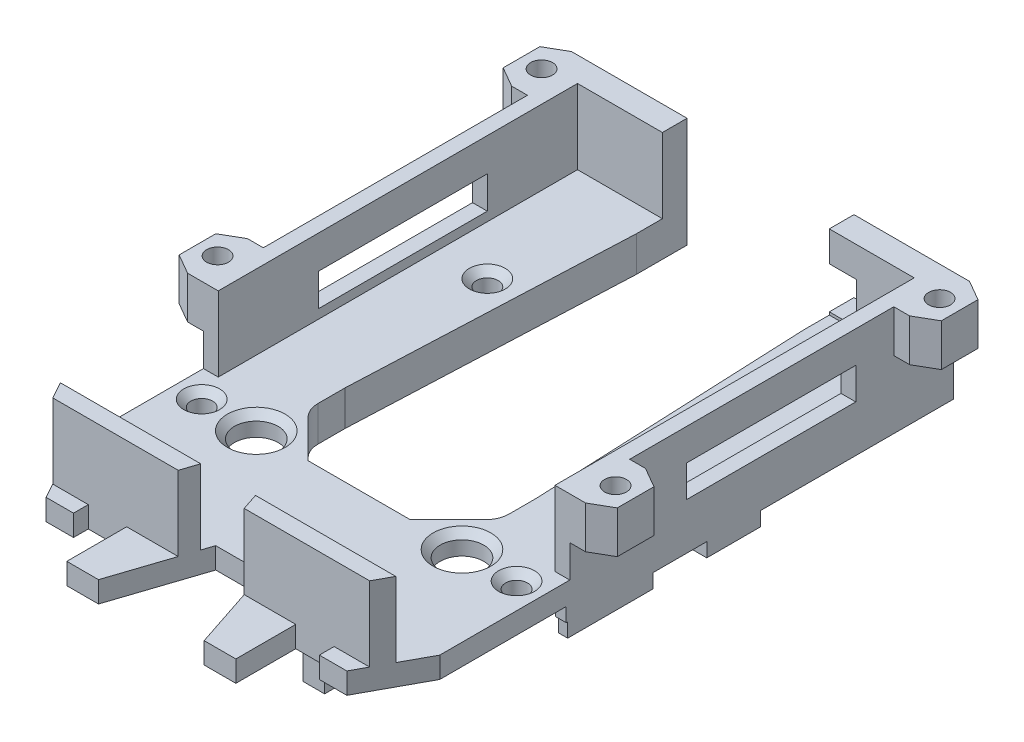
SolidWorks part; units mm, degrees
other "细节项目1"
material "PPS"
ref_plane "前视基准面" through (0, 0, 0) normal (0, 0, 1) x (1, 0, 0)
ref_plane "上视基准面" through (0, 0, 0) normal (0, 1, 0) x (1, 0, 0)
ref_plane "右视基准面" through (0, 0, 0) normal (1, 0, 0) x (0, 0, -1)
sketch "轮廓参考-草图" plane through (0, 0, 0) normal (0, 1, 0) x (1, 0, 0)
  line L0 (-126.4995, 0) -> (116.8967, 0) construction
  line L2 (0, 104.5414) -> (0, -99.6328) construction
  line L25 (24.5, -95.1) -> (26.0011, -95.1) construction
  line L38 (-16.7464, -105.1066) -> (-17.9066, -103.9464) construction
  line L42 (26.0011, -95.1) -> (26.0011, -102.35)
  line L72 (26.0011, -102.35) -> (22.5, -102.35)
  line L80 (-18.6137, -103.9464) -> (-19.7036, -105.0363) construction
  line L82 (4.1009, -74) -> (4.1009, -71.0475)
  line L83 (-3.6009, -74.5) -> (3.6009, -74.5)
  line L86 (-4.1009, -74) -> (-4.1009, -71.0461)
  line L88 (-4.8984, -70.3461) -> (-4.8009, -70.3461)
  line L91 (4.8009, -70.3475) -> (4.8984, -70.3475)
  line L98 (19, -100.5) -> (-19, -100.5) construction
  line L100 (22.5, -102.35) -> (22.5, -110.35)
  line L101 (16.1, -146) -> (16.1, -154.5)
  line L102 (16.1, -146) -> (12, -146)
  line L103 (12, -146) -> (12, -163)
  line L104 (17.45, -154.5) -> (16.1, -154.5)
  line L105 (17.45, -156.6) -> (17.45, -154.5)
  line L106 (-3.3584, -150.5) -> (-7.5, -163)
  line L107 (-7.5, -163) -> (-12, -163)
  line L108 (21.3534, -156.6) -> (17.45, -156.6)
  line L109 (-17.45, -156.6) -> (-17.45, -154.5)
  line L110 (-17.45, -154.5) -> (-16.1, -154.5)
  line L111 (-12, -146) -> (-12, -163)
  line L112 (-16.1, -146) -> (-12, -146)
  line L113 (-16.1, -146) -> (-16.1, -154.5)
  line L114 (7.5, -163) -> (12, -163)
  line L115 (-3.3584, -150.5) -> (3.3584, -150.5)
  line L116 (3.3584, -150.5) -> (7.5, -163)
  line L117 (-21.3534, -156.6) -> (-17.45, -156.6)
  line L118 (-13.5761, -121.8546) -> (-11.8487, -82.2911)
  line L119 (-12.5918, -128.1539) -> (-7.25, -133.5)
  line L120 (-7.25, -133.5) -> (7.25, -133.5)
  line L121 (-13.5793, -125.7684) -> (-13.5793, -122.0018)
  line L122 (22.5, -110.35) -> (26.0011, -110.35)
  line L123 (26.0011, -130.1) -> (26.0011, -148.0463)
  line L124 (26.0011, -148.0463) -> (21.3534, -156.6)
  line L125 (-26.0011, -148.0463) -> (-21.3534, -156.6)
  line L126 (-26.0011, -130.1) -> (-26.0011, -148.0463)
  line L127 (26.0011, -110.35) -> (26.0011, -117.6)
  line L128 (26.0011, -117.6) -> (24.5011, -117.6)
  line L129 (24.5011, -117.6) -> (24.5011, -130.1)
  line L130 (24.5011, -130.1) -> (26.0011, -130.1)
  line L132 (-24.5011, -130.1) -> (-26.0011, -130.1)
  line L133 (-24.5011, -117.6) -> (-24.5011, -130.1)
  line L134 (-26.0011, -117.6) -> (-24.5011, -117.6)
  line L135 (-26.0011, -110.35) -> (-26.0011, -117.6)
  line L136 (-22.5, -110.35) -> (-26.0011, -110.35)
  line L137 (-22.5, -102.35) -> (-22.5, -110.35)
  line L138 (-26.0011, -102.35) -> (-22.5, -102.35)
  line L139 (-26.0011, -95.1) -> (-26.0011, -102.35)
  line L140 (-24.5, -95.1) -> (-26.0011, -95.1) construction
  line L150 (0, -114.8485) -> (0, -146.3095) construction
  line L151 (-10.5, -81) -> (10.5, -81)
  line L152 (12.5918, -128.1539) -> (7.25, -133.5)
  line L153 (13.5793, -125.7684) -> (13.5793, -122.0018)
  line L154 (13.5761, -121.8546) -> (11.8487, -82.2911)
  line L203 (26.0011, -95.1) -> (38.6804, -95.1)
  line L204 (38.6804, -95.1) -> (38.6804, -86.6)
  line L205 (38.6804, -86.6) -> (24.5, -79.9478)
  line L207 (-38.6804, -86.6) -> (-24.5, -79.9478)
  line L208 (-38.6804, -95.1) -> (-38.6804, -86.6)
  line L209 (-26.0011, -95.1) -> (-38.6804, -95.1)
  line L211 (-19.7036, -114.2434) -> (-18.5434, -115.4036) construction
  line L212 (-17.8363, -115.4036) -> (-16.7464, -114.3137) construction
  line L213 (-19.85, -105.3898) -> (-19.85, -113.8898) construction
  line L214 (-16.6, -105.4602) -> (-16.6, -113.9602) construction
  line L221 (-16.6, -105.4602) -> (-16.6, -108.5148) construction
  line L222 (-16.6, -108.5148) -> (-17.1, -109.0148) construction
  line L223 (-17.1, -109.0148) -> (-17.1, -110.2648) construction
  line L224 (-17.1, -110.2648) -> (-16.6, -110.7648) construction
  line L225 (-16.6, -110.7648) -> (-16.6, -113.9602) construction
  line L226 (-19.85, -109.6398) -> (-13.2317, -109.6398) construction
  line L227 (17.1, -110.2648) -> (16.6, -110.7648) construction
  line L228 (17.1, -109.0148) -> (17.1, -110.2648) construction
  line L229 (16.6, -108.5148) -> (17.1, -109.0148) construction
  line L230 (16.6, -105.4602) -> (16.6, -108.5148) construction
  line L231 (16.7464, -105.1066) -> (17.9066, -103.9464) construction
  line L232 (18.6137, -103.9464) -> (19.7036, -105.0363) construction
  line L233 (19.85, -105.3898) -> (19.85, -113.8898) construction
  line L234 (19.7036, -114.2434) -> (18.5434, -115.4036) construction
  line L235 (17.8363, -115.4036) -> (16.7464, -114.3137) construction
  line L236 (16.6, -110.7648) -> (16.6, -113.9602) construction
  line L237 (-24.5, -72.3717) -> (-22.5, -72.3717)
  line L238 (-22.5, -72.3717) -> (-22.5, -79.9478)
  line L239 (-22.5, -79.9478) -> (-24.5, -79.9478)
  line L241 (22.5, -79.9478) -> (24.5, -79.9478)
  line L243 (24.5, -72.3717) -> (22.5, -72.3717)
  line L244 (22.5, -72.3717) -> (22.5, -79.9478)
  arc A82 (-16.6, -105.4602) -> (-16.7464, -105.1066) centre (-17.1, -105.4602) ccw construction
  arc A83 (-17.9066, -103.9464) -> (-18.6137, -103.9464) centre (-18.2602, -104.3) ccw construction
  arc A84 (-19.85, -105.3898) -> (-19.7036, -105.0363) centre (-19.35, -105.3898) cw construction
  arc A85 (-4.1009, -74) -> (-3.6009, -74.5) centre (-4.1009, -74.5) ccw
  arc A86 (4.1009, -74) -> (3.6009, -74.5) centre (4.1009, -74.5) cw
  arc A94 (4.1009, -71.0475) -> (4.8009, -70.3475) centre (4.8009, -71.0475) cw
  arc A96 (-4.1009, -71.0461) -> (-4.8009, -70.3461) centre (-4.8009, -71.0461) ccw
  circle A103 centre (-22.35, -133.5) radius 1.55
  circle A104 centre (22.35, -133.5) radius 1.55
  circle A105 centre (-16.9, -98.4) radius 1.55
  circle A106 centre (16.9, -98.4) radius 1.55
  arc A107 (-10.5, -81) -> (-11.8487, -82.2911) centre (-10.5, -82.35) ccw
  arc A108 (-13.5793, -122.0018) -> (-13.5761, -121.8546) centre (-10.2043, -122.0018) cw
  arc A109 (-12.5918, -128.1539) -> (-13.5793, -125.7684) centre (-10.2043, -125.7684) cw
  circle A110 centre (-14.6, -133.5) radius 1.55
  circle A111 centre (14.6, -133.5) radius 1.55
  arc A112 (12.5918, -128.1539) -> (13.5793, -125.7684) centre (10.2043, -125.7684) ccw
  arc A113 (13.5793, -122.0018) -> (13.5761, -121.8546) centre (10.2043, -122.0018) ccw
  arc A114 (10.5, -81) -> (11.8487, -82.2911) centre (10.5, -82.35) cw
  circle A146 centre (0, -76.75) radius 1.55
  circle A188 centre (34.5, -90.85) radius 1.55
  circle A189 centre (-34.5, -90.85) radius 1.55
  arc A192 (-19.85, -113.8898) -> (-19.7036, -114.2434) centre (-19.35, -113.8898) ccw construction
  arc A193 (-18.5434, -115.4036) -> (-17.8363, -115.4036) centre (-18.1898, -115.05) ccw construction
  arc A194 (-16.6, -113.9602) -> (-16.7464, -114.3137) centre (-17.1, -113.9602) cw construction
  arc A195 (16.6, -105.4602) -> (16.7464, -105.1066) centre (17.1, -105.4602) cw construction
  arc A196 (17.9066, -103.9464) -> (18.6137, -103.9464) centre (18.2602, -104.3) cw construction
  arc A197 (19.85, -105.3898) -> (19.7036, -105.0363) centre (19.35, -105.3898) ccw construction
  arc A198 (19.85, -113.8898) -> (19.7036, -114.2434) centre (19.35, -113.8898) cw construction
  arc A199 (18.5434, -115.4036) -> (17.8363, -115.4036) centre (18.1898, -115.05) cw construction
  arc A200 (16.6, -113.9602) -> (16.7464, -114.3137) centre (17.1, -113.9602) ccw construction
  point P2 (0, 0)
  point P3 (0, 0)
  point P5 (0, 0)
  point P7 (0, 0)
  point P8 (0, 0)
  point P9 (0, 0)
  point P10 (0, 0)
  point P11 (0, 0)
  point P12 (0, 0)
  point P13 (0, 0)
  point P14 (0, 0)
  point P15 (0, 0)
  point P16 (0, 0)
  point P17 (0, 0)
  point P18 (0, 0)
  point P19 (0, 0)
  point P214 (38.6804, -90.85)
  point P354 (0, -133.5)
  point P361 (7.3036, -118.1341)
  point P364 (0, -81)
  dimension "D22" = 3.1
  dimension "D32" = 7.25
  dimension "D15" = 3.25
  dimension "D13" = 19.85
  dimension "D9" = 3.1
  dimension "D59" = 8.5
  dimension "D23" = 2.25
  dimension "D33" = 1.5
  dimension "D34" = 2.1
  dimension "D35" = 8.5
  dimension "D36" = 4.5
  dimension "D37" = 4
  dimension "D38" = 4.1
  dimension "D39" = 8
  dimension "D42" = 10.5
  dimension "D44" = 52.5
  dimension "D58" = 34.5
  dimension "D62" = 7.25
  dimension "D64" = 8.5
  dimension "D65" = 1.25
  dimension "D66" = 0.5
  dimension "D72" = 29.2
  dimension "D73" = 7.75
  dimension "D74" = 1.35
  dimension "D75" = 24
  dimension "D76" = 6.4
  dimension "D77" = 12.5
  dimension "D78" = 6.5
  dimension "D79" = 92.5
  dimension "D80" = 12.5
  dimension "D81" = 133.5
  dimension "D82" = 4.5
sketch "防撞圈参考-草图" plane through (0, 0, 0) normal (0, 1, 0) x (1, 0, 0)
  line L0 (0, -816.4831) -> (0, 39952.7477) construction
  line L204 (0.25, -133.5) -> (0.25, -150.5)
  line L206 (0.25, -150.5) -> (3.3584, -150.5)
  line L207 (3.3584, -150.5) -> (7.5, -163)
  line L241 (0.25, -133.5) -> (7.25, -133.5)
  line L242 (7.25, -133.5) -> (12.5918, -128.1539)
  line L243 (12.5918, -128.1539) -> (24.5011, -128.1539)
  line L245 (0, 0) -> (303.0286, 0) construction
  line L248 (17.45, -156.6) -> (21.3534, -156.6)
  line L249 (7.5, -163) -> (12, -163)
  line L250 (12, -163) -> (12, -146)
  line L251 (12, -146) -> (16.1, -146)
  line L252 (16.1, -146) -> (16.1, -154.5)
  line L253 (16.1, -154.5) -> (17.45, -154.5)
  line L254 (17.45, -154.5) -> (17.45, -156.6)
  line L256 (24.5011, -128.1539) -> (24.5011, -130.1)
  line L257 (24.5011, -130.1) -> (26.0011, -130.1)
  line L258 (26.0011, -130.1) -> (26.0011, -139.0732)
  line L260 (26.0011, -139.0732) -> (48.4165, -143.309)
  line L269 (21.3534, -156.6) -> (48.4165, -157.809)
  circle A96 centre (14.6, -133.5) radius 1.55
  circle A103 centre (22.35, -133.5) radius 1.55
  dimension "D8" = 0.25
sketch "底座草图" plane through (0, 0, 0) normal (0, 1, 0) x (1, 0, 0)
  line L1 (0, 0) -> (177.3778, 0) construction
  line L21 (0, 0) -> (0, -206.0734) construction
  line L98 (-24.5011, -125.0264) -> (-17.0421, -115.35)
  line L106 (-3.3584, -150.5) -> (-7.5, -163)
  line L107 (-7.5, -163) -> (-12, -163)
  line L109 (-17.45, -156.6) -> (-17.45, -154.5)
  line L110 (-17.45, -154.5) -> (-16.1, -154.5)
  line L111 (-12, -146) -> (-12, -163)
  line L112 (-16.1, -146) -> (-12, -146)
  line L113 (-16.1, -146) -> (-16.1, -154.5)
  line L117 (-21.3534, -156.6) -> (-17.45, -156.6)
  line L125 (-26.0011, -148.0463) -> (-21.3534, -156.6)
  line L126 (-26.0011, -130.1) -> (-26.0011, -148.0463)
  line L132 (-24.5011, -130.1) -> (-26.0011, -130.1) construction
  line L157 (-24.5011, -117.6) -> (-24.5011, -130.1) construction
  line L158 (-26.0011, -117.6) -> (-24.5011, -117.6) construction
  line L162 (-24.5011, -125.0264) -> (-26.0011, -126.6)
  line L163 (-26.0011, -126.6) -> (-26.0011, -130.1)
  line L171 (-3.3584, -150.5) -> (3.3584, -150.5)
  line L177 (-13.5761, -121.8546) -> (-11.8487, -82.2911) construction
  line L181 (-12.5918, -128.1539) -> (-7.25, -133.5)
  line L191 (24.5011, -125.0264) -> (17.0421, -115.35)
  line L192 (24.5011, -125.0264) -> (26.0011, -126.6)
  line L193 (26.0011, -126.6) -> (26.0011, -130.1)
  line L194 (26.0011, -130.1) -> (26.0011, -148.0463)
  line L195 (26.0011, -148.0463) -> (21.3534, -156.6)
  line L196 (21.3534, -156.6) -> (17.45, -156.6)
  line L197 (17.45, -154.5) -> (16.1, -154.5)
  line L198 (16.1, -146) -> (16.1, -154.5)
  line L199 (16.1, -146) -> (12, -146)
  line L200 (12, -146) -> (12, -163)
  line L201 (7.5, -163) -> (12, -163)
  line L202 (3.3584, -150.5) -> (7.5, -163)
  line L204 (17.45, -156.6) -> (17.45, -154.5)
  line L211 (-7.25, -133.5) -> (7.25, -133.5)
  line L212 (-13.5793, -125.7684) -> (-13.5793, -122.0018)
  line L213 (-10.5, -81) -> (10.5, -81) construction
  line L214 (12.5918, -128.1539) -> (7.25, -133.5)
  line L215 (13.5793, -125.7684) -> (13.5793, -122.0018)
  line L216 (13.5761, -121.8546) -> (11.8487, -82.2911) construction
  line L217 (-17.0421, -115.35) -> (-13.2921, -115.35)
  line L218 (-13.5793, -122.0018) -> (-13.5761, -121.8546)
  line L220 (13.5793, -122.0018) -> (13.5761, -121.8546)
  line L222 (-13.2921, -115.35) -> (-13.5761, -121.8546)
  line L224 (17.0421, -115.35) -> (13.2921, -115.35)
  line L225 (13.2921, -115.35) -> (13.5761, -121.8546)
  line L226 (-7.25, -133.5) -> (7.25, -133.5) construction
  line L227 (-26.0011, -117.6) -> (-24.5011, -117.6) construction
  line L228 (-24.5011, -130.1) -> (-26.0011, -130.1) construction
  line L229 (-3.3584, -150.5) -> (3.3584, -150.5) construction
  line L230 (-3.3584, -150.5) -> (-7.5, -163) construction
  line L231 (-7.5, -163) -> (-12, -163) construction
  line L232 (-12, -146) -> (-12, -163) construction
  line L233 (-16.1, -146) -> (-16.1, -154.5) construction
  line L234 (-17.45, -154.5) -> (-16.1, -154.5) construction
  line L236 (-17.45, -156.6) -> (-17.45, -154.5) construction
  line L238 (-21.3534, -156.6) -> (-17.45, -156.6) construction
  line L239 (-26.0011, -148.0463) -> (-21.3534, -156.6) construction
  line L240 (-16.1, -146) -> (-12, -146) construction
  line L241 (-26.0011, -130.1) -> (-26.0011, -148.0463) construction
  line L242 (-12.5918, -128.1539) -> (-7.25, -133.5) construction
  line L243 (-13.5793, -125.7684) -> (-13.5793, -122.0018) construction
  line L244 (-13.5761, -121.8546) -> (-11.8487, -82.2911) construction
  line L245 (13.5761, -121.8546) -> (11.8487, -82.2911) construction
  line L246 (-10.5, -81) -> (10.5, -81) construction
  line L247 (-24.5011, -117.6) -> (-24.5011, -130.1) construction
  line L248 (13.5793, -125.7684) -> (13.5793, -122.0018) construction
  line L249 (-26.0011, -110.35) -> (-26.0011, -117.6) construction
  circle A103 centre (-22.35, -133.5) radius 1.55
  circle A110 centre (-14.6, -133.5) radius 3.1
  circle A117 centre (14.6, -133.5) radius 3.1
  circle A118 centre (22.35, -133.5) radius 1.55
  arc A123 (-10.5, -81) -> (-11.8487, -82.2911) centre (-10.5, -82.35) ccw construction
  arc A124 (-12.5918, -128.1539) -> (-13.5793, -125.7684) centre (-10.2043, -125.7684) cw
  arc A126 (12.5918, -128.1539) -> (13.5793, -125.7684) centre (10.2043, -125.7684) ccw
  arc A127 (10.5, -81) -> (11.8487, -82.2911) centre (10.5, -82.35) cw construction
  circle A128 centre (-22.35, -133.5) radius 1.55 construction
  point P7 (0, -133.5)
  point P15 (0, 0)
  point P26 (0, -81)
  point P93 (0, 0)
  point P96 (-12.3254, -128.4205)
  point P101 (11.8442, -82.2249)
  point P103 (0, 0)
  point P104 (0, 0)
  point P105 (0, 0)
  point P106 (0, 0)
  point P107 (0, 0)
  point P110 (-12.5918, -133.5)
  point P111 (0, 0)
  point P112 (0, 0)
  point P113 (0, 0)
  point P114 (13.5793, -122.2557)
  point P117 (0, 0)
  point P118 (0, 0)
  point P119 (0, 0)
  point P122 (0, 0)
  point P123 (-24.5011, -125.4781)
  point P124 (-24.5011, -124.979)
  point P125 (-24.5011, -125.0264)
  point P126 (0, 0)
  dimension "D2" = 136.372
  dimension "D5" = 6.2
  dimension "D1" = 2.25
  dimension "D3" = 3.5
  dimension "D4" = 3.75
extrude "基座_3mm_留线槽空间1.5mm" add sketch "底座草图" along normal blind 3
sketch "Sketch2" plane through (0, 0, 0) normal (0, 1, 0) x (1, 0, 0)
  line L1 (0, 0) -> (177.3778, 0) construction
  line L21 (0, 0) -> (0, -206.0734) construction
  line L98 (-24.5011, -125.0264) -> (-17.0421, -115.35)
  line L106 (-3.3584, -150.5) -> (-7.5, -163) construction
  line L107 (-7.5, -163) -> (-12, -163) construction
  line L109 (-17.45, -156.6) -> (-17.45, -154.5) construction
  line L110 (-17.45, -154.5) -> (-16.1, -154.5) construction
  line L111 (-12, -146) -> (-12, -163) construction
  line L112 (-16.1, -146) -> (-12, -146) construction
  line L113 (-16.1, -146) -> (-16.1, -154.5) construction
  line L117 (-21.3534, -156.6) -> (-17.45, -156.6) construction
  line L125 (-26.0011, -148.0463) -> (-21.3534, -156.6) construction
  line L126 (-26.0011, -130.1) -> (-26.0011, -148.0463) construction
  line L162 (-24.5011, -125.0264) -> (-26.0011, -126.6)
  line L163 (-26.0011, -126.6) -> (-26.0011, -130.1) construction
  line L171 (-3.3584, -150.5) -> (3.3584, -150.5) construction
  line L177 (-13.5761, -121.8546) -> (-11.8487, -82.2911) construction
  line L181 (-12.5918, -128.1539) -> (-7.25, -133.5) construction
  line L191 (24.5011, -125.0264) -> (17.0421, -115.35)
  line L192 (24.5011, -125.0264) -> (26.0011, -126.6)
  line L193 (26.0011, -126.6) -> (26.0011, -130.1) construction
  line L194 (26.0011, -130.1) -> (26.0011, -148.0463) construction
  line L195 (26.0011, -148.0463) -> (21.3534, -156.6) construction
  line L196 (21.3534, -156.6) -> (17.45, -156.6) construction
  line L197 (17.45, -154.5) -> (16.1, -154.5) construction
  line L198 (16.1, -146) -> (16.1, -154.5) construction
  line L199 (16.1, -146) -> (12, -146) construction
  line L200 (12, -146) -> (12, -163) construction
  line L201 (7.5, -163) -> (12, -163) construction
  line L202 (3.3584, -150.5) -> (7.5, -163) construction
  line L204 (17.45, -156.6) -> (17.45, -154.5) construction
  line L211 (-7.25, -133.5) -> (7.25, -133.5) construction
  line L212 (-13.5793, -125.7684) -> (-13.5793, -122.0018) construction
  line L213 (-10.5, -81) -> (10.5019, -81) construction
  line L214 (12.5918, -128.1539) -> (7.25, -133.5) construction
  line L215 (13.5793, -125.7684) -> (13.5793, -122.0018) construction
  line L216 (13.5761, -121.8546) -> (11.8487, -82.2911) construction
  line L217 (-17.0421, -115.35) -> (-13.2921, -115.35)
  line L218 (-13.5793, -122.0018) -> (-13.5761, -121.8546) construction
  line L220 (13.5793, -122.0018) -> (13.5761, -121.8546) construction
  line L222 (-13.2921, -115.35) -> (-13.5761, -121.8546) construction
  line L224 (17.0421, -115.35) -> (13.2921, -115.35)
  line L225 (13.2921, -115.35) -> (13.5761, -121.8546) construction
  line L246 (-24.5011, -130.1) -> (-26.0011, -130.1) construction
  line L247 (-24.5011, -117.6) -> (-24.5011, -130.1) construction
  line L248 (-26.0011, -117.6) -> (-24.5011, -117.6) construction
  line L249 (-26.0011, -110.35) -> (-26.0011, -117.6) construction
  line L250 (-22.5, -110.35) -> (-26.0011, -110.35) construction
  line L251 (-22.5, -102.35) -> (-22.5, -110.35) construction
  line L252 (-26.0011, -102.35) -> (-22.5, -102.35) construction
  line L253 (-26.0011, -75.1) -> (-26.0011, -102.35) construction
  line L255 (24.5011, -130.1) -> (26.0011, -130.1) construction
  line L256 (24.5011, -117.6) -> (24.5011, -130.1) construction
  line L257 (26.0011, -117.6) -> (24.5011, -117.6) construction
  line L259 (26.0011, -75.1) -> (26.0011, -102.35) construction
  line L260 (26.0011, -102.35) -> (22.5, -102.35) construction
  line L261 (22.5, -102.35) -> (22.5, -110.35) construction
  line L262 (22.5, -110.35) -> (26.0011, -110.35) construction
  line L266 (-11.8487, -82.2911) -> (-13.2921, -115.35) construction
  line L267 (13.2921, -115.35) -> (11.8487, -82.2911) construction
  line L273 (-13.2921, -115.35) -> (-11.8487, -82.2911)
  line L276 (11.8487, -82.2911) -> (13.2921, -115.35)
  line L287 (-26.0011, -75.1) -> (-26.0011, -126.6)
  line L288 (-26.0011, -75.1) -> (-11.8487, -75.1)
  line L289 (-11.8487, -75.1) -> (-11.8487, -82.2911)
  line L290 (26.0011, -75.1) -> (26.0011, -126.6)
  line L291 (26.0011, -75.1) -> (11.8487, -75.1)
  line L292 (11.8487, -75.1) -> (11.8487, -82.2911)
  line L293 (-13.2921, -115.35) -> (-17.0421, -115.35) construction
  line L294 (-3.3584, -150.5) -> (3.3584, -150.5) construction
  line L295 (-3.3584, -150.5) -> (-7.5, -163) construction
  line L296 (-12, -146) -> (-12, -163) construction
  line L298 (-16.1, -146) -> (-12, -146) construction
  line L299 (-16.1, -146) -> (-16.1, -154.5) construction
  line L300 (-17.45, -154.5) -> (-16.1, -154.5) construction
  line L301 (-21.3534, -156.6) -> (-17.45, -156.6) construction
  line L302 (-17.45, -156.6) -> (-17.45, -154.5) construction
  line L303 (-26.0011, -148.0463) -> (-21.3534, -156.6) construction
  line L304 (-26.0011, -130.1) -> (-26.0011, -148.0463) construction
  line L305 (-24.5011, -130.1) -> (-26.0011, -130.1) construction
  line L306 (0, 104.5414) -> (0, -99.6328) construction
  line L307 (-126.4995, 0) -> (116.8967, 0) construction
  line L308 (-12.5918, -128.1539) -> (-7.25, -133.5) construction
  line L309 (-7.25, -133.5) -> (7.25, -133.5) construction
  line L310 (12.5918, -128.1539) -> (7.25, -133.5) construction
  line L311 (-13.5761, -121.8546) -> (-11.8487, -82.2911) construction
  circle A103 centre (-22.35, -133.5) radius 1.55 construction
  circle A110 centre (-14.6, -133.5) radius 3.1 construction
  circle A117 centre (14.6, -133.5) radius 3.1 construction
  circle A118 centre (22.35, -133.5) radius 1.55 construction
  arc A123 (-10.5, -81) -> (-11.8487, -82.2911) centre (-10.5, -82.35) ccw construction
  arc A124 (-12.5918, -128.1539) -> (-13.5793, -125.7684) centre (-10.2043, -125.7684) cw construction
  arc A126 (12.5918, -128.1539) -> (13.5793, -125.7684) centre (10.2043, -125.7684) ccw construction
  arc A127 (10.5, -81) -> (11.8487, -82.2911) centre (10.5, -82.35) cw construction
  circle A129 centre (-16.9, -98.4) radius 1.55
  circle A130 centre (16.9, -98.4) radius 1.55
  circle A131 centre (-14.6, -133.5) radius 3.1 construction
  circle A132 centre (-22.35, -133.5) radius 1.55 construction
  circle A133 centre (-16.9, -98.4) radius 1.55 construction
  point P7 (0, -133.5)
  point P26 (0.0009, -81)
  point P89 (-12, -163)
  point P91 (0, 0)
  point P107 (-24.5011, -130.1)
  point P108 (-24.5011, -117.6)
  point P109 (-26.0011, -117.6)
  point P110 (-24.5011, -125.0264)
  point P111 (-26.0011, -126.6)
  point P112 (-17.0421, -115.35)
  point P115 (-26.0011, -130.1)
  point P118 (-26.0011, -130.076)
  point P123 (0, 0)
  point P134 (-11.8496, -128.913)
  point P135 (0, 0)
  point P136 (0, 0)
  point P137 (-13.4901, -121.8768)
  point P138 (-13.5793, -122.0289)
  point P139 (0, 0)
  point P140 (0, 0)
  point P143 (-11.8487, -82.2911)
  point P144 (-10.5, -81)
  point P145 (0, 0)
  point P146 (0, 0)
  point P147 (13.5793, -125.7684)
  point P148 (-26.0011, -102.35)
  point P149 (-22.5, -102.35)
  point P150 (-26.0011, -110.35)
  point P151 (-22.5, -110.35)
  point P152 (0, 0)
  point P153 (-26.0011, -75.7704)
  dimension "D1" = 51.5
sketch "底部配平-草图" plane through (0, 0, 0) normal (0, 1, 0) x (1, 0, 0)
  line L0 (13.2921, -115.35) -> (17.0421, -115.35)
  line L1 (17.0421, -115.35) -> (24.5011, -125.0264)
  line L2 (24.5011, -125.0264) -> (24.5011, -128.1539)
  line L3 (24.5011, -128.1539) -> (12.5918, -128.1539)
  line L4 (13.5793, -125.7684) -> (13.5793, -122.0018)
  line L5 (13.2921, -115.35) -> (13.5761, -121.8546)
  line L6 (0, 0) -> (0, -182.2941) construction
  line L7 (0, -200816.4831) -> (0, 239952.7477) construction
  line L8 (-13.2921, -115.35) -> (-13.5761, -121.8546)
  line L9 (-13.5793, -125.7684) -> (-13.5793, -122.0018)
  line L10 (-24.5011, -128.1539) -> (-12.5918, -128.1539)
  line L11 (-24.5011, -125.0264) -> (-24.5011, -128.1539)
  line L12 (-17.0421, -115.35) -> (-24.5011, -125.0264)
  line L13 (-13.2921, -115.35) -> (-17.0421, -115.35)
  arc A0 (13.5793, -125.7684) -> (12.5918, -128.1539) centre (10.2043, -125.7684) cw
  arc A1 (12.5918, -128.1539) -> (13.5793, -125.7684) centre (10.2043, -125.7684) ccw construction
  arc A2 (13.5761, -121.8546) -> (13.5793, -122.0018) centre (10.2043, -122.0018) cw
  arc A3 (-13.5761, -121.8546) -> (-13.5793, -122.0018) centre (-10.2043, -122.0018) ccw
  arc A4 (-13.5793, -125.7684) -> (-12.5918, -128.1539) centre (-10.2043, -125.7684) ccw
extrude "底部配平" add sketch "底部配平-草图" against normal blind 2
sketch "草图5" plane through (0, 0, 0) normal (0, 1, 0) x (1, 0, 0)
  line L1 (0, 0) -> (-145.7487, 0) construction
  line L21 (0, 0) -> (0, -197.5016) construction
  line L182 (-16.1, -146) -> (-12, -146)
  line L183 (-12, -146) -> (-12, -154.5)
  line L184 (-12, -146) -> (-12, -163) construction
  line L185 (-12, -154.5) -> (-16.1, -154.5)
  line L186 (-16.1, -154.5) -> (-16.1, -146) construction
  line L187 (-16.1, -154.5) -> (-16.1, -146)
  line L189 (-15.6, -146.5) -> (-12.5, -146.5)
  line L190 (-12.5, -146.5) -> (-12.5, -154)
  line L191 (-12.5, -154) -> (-15.6, -154)
  line L192 (-15.6, -154) -> (-15.6, -146.5)
  line L194 (15.6, -154) -> (15.6, -146.5)
  line L195 (12.5, -154) -> (15.6, -154)
  line L196 (12.5, -146.5) -> (12.5, -154)
  line L197 (15.6, -146.5) -> (12.5, -146.5)
  line L198 (16.1, -154.5) -> (16.1, -146)
  line L199 (12, -154.5) -> (16.1, -154.5)
  line L200 (12, -146) -> (12, -154.5)
  line L201 (16.1, -146) -> (12, -146)
  line L206 (-24.5011, -125.0264) -> (-26.0011, -126.6) construction
  line L214 (-24.5011, -125.0264) -> (-26.0011, -126.6) construction
  line L215 (-26.0011, -126.6) -> (-26.0011, -130.1) construction
  line L217 (-26.0011, -130.1) -> (-24.5011, -130.1) construction
  line L218 (-24.5011, -130.1) -> (-24.5011, -125.0264) construction
  line L219 (-24.5011, -130.1) -> (-26.0011, -130.1) construction
  line L220 (-24.5011, -117.6) -> (-24.5011, -130.1) construction
  line L225 (-24.7011, -125.2362) -> (-24.7011, -129.9)
  line L226 (-24.7011, -129.9) -> (-26.0011, -129.9)
  line L230 (24.7011, -125.2362) -> (24.7011, -129.9)
  line L231 (24.7011, -129.9) -> (26.0011, -129.9)
  line L232 (-24.7011, -125.2362) -> (-26.0011, -126.6)
  line L233 (-26.0011, -126.6) -> (-26.0011, -129.9)
  line L235 (24.7011, -125.2362) -> (26.0011, -126.6)
  line L236 (26.0011, -126.6) -> (26.0011, -129.9)
  line L238 (-24.7011, -125.2362) -> (-24.5011, -125.0264)
  line L239 (-24.5011, -125.0264) -> (-24.5011, -130.1)
  line L240 (-24.5011, -130.1) -> (-26.0011, -130.1)
  line L241 (-26.0011, -130.1) -> (-26.0011, -129.9)
  line L243 (24.7011, -125.2362) -> (24.5011, -125.0264)
  line L244 (24.5011, -125.0264) -> (24.5011, -130.1)
  line L245 (24.5011, -130.1) -> (26.0011, -130.1)
  line L246 (26.0011, -130.1) -> (26.0011, -129.9)
  dimension "D2" = 0.2
  dimension "D5" = 0.5
  dimension "D7" = 0.5
  dimension "D8" = 0.5
  dimension "D6" = 0.5
  dimension "D1" = 0.2
extrude "结构填充" add sketch "草图5" along normal up to surface (3 mm away) contours L192 L191 L190 L189 | L187 L185 L183 L182 L191 L192 L189 L190 | L194 L197 L196 L195 | L198 L201 L200 L199 L197 L194 L195 L196 | L232 L233 L226 L225 | L241 L240 L239 L238 L225 L226 | L236 L235 L230 L231 | L245 L246 L231 L230 L243 L244 region at (-14.05, 0, 146.0944) region at (-14.05, 0, 150.25) region at (14.05, 0, 150.25) region at (14.05, 0, 154.4056) region at (-24.5628, 0, 125.1678) region at (-25.314, 0, 127.8896) region at (25.314, 0, 127.8896) region at (24.6482, 0, 127.5681) up to face at (0, 3, 139.6026)
extrude "结构填充-2" add sketch "草图5<6>" against normal up to surface (2 mm away) contours L236 L235 L230 L231 | L245 L246 L231 L230 L243 L244 | L232 L233 L226 L225 | L241 L240 L239 L238 L225 L226 region at (-24.5628, 0, 125.1678) region at (-25.314, 0, 127.8896) region at (25.314, 0, 127.8896) region at (24.6482, 0, 127.5681) up to face at (16.6126, -2, 122.7197)
sketch "草图5<6>" plane through (0, 0, 0) normal (0, 1, 0) x (1, 0, 0) same geometry as "草图5"
extrude "限位卡榫" add sketch "草图5<5>" against normal offset from surface (7 mm away) 4 from surface contours L192 L191 L190 L189 | L194 L197 L196 L195 | L217 L218 L214 L215 | L232 L233 L226 L225 | L236 L235 L230 L231 region at (-14.05, 0, 150.25) region at (14.05, 0, 150.25) region at (-25.314, 0, 127.8896) region at (25.314, 0, 127.8896) up to face at (-14.6, 0, 130.4) offset beyond the face yes starting at face at (0, 3, 138.85)
sketch "草图5<5>" plane through (0, 0, 0) normal (0, 1, 0) x (1, 0, 0) same geometry as "草图5"
extrude "基座扩展" add sketch "Sketch2" along normal blind 3 and the other way blind 2
sketch "Sketch3" plane through (0, 0, 0) normal (0, 1, 0) x (1, 0, 0)
  line L1 (0, 0) -> (177.3778, 0) construction
  line L21 (0, 0) -> (0, -206.0734) construction
  line L177 (0, 104.5414) -> (0, -99.6328) construction
  line L246 (-126.4995, 0) -> (116.8967, 0) construction
  line L247 (26.0011, -102.55) -> (26.0011, -110.15)
  line L248 (-26.0011, -117.6) -> (-24.5011, -117.6)
  line L249 (-26.0011, -102.55) -> (-22.7, -102.55)
  line L250 (-22.5, -110.35) -> (-26.0011, -110.35)
  line L251 (-22.5, -102.35) -> (-22.5, -110.35)
  line L252 (-26.0011, -102.35) -> (-22.5, -102.35)
  line L253 (-26.0011, -102.55) -> (-26.0011, -110.15)
  line L257 (26.0011, -117.6) -> (24.5011, -117.6)
  line L259 (-26.0011, -110.15) -> (-22.7, -110.15)
  line L260 (26.0011, -102.35) -> (22.5, -102.35)
  line L261 (22.5, -102.35) -> (22.5, -110.35)
  line L262 (22.5, -110.35) -> (26.0011, -110.35)
  line L277 (-24.5011, -117.6) -> (-24.5011, -130.1)
  line L278 (-24.5011, -130.1) -> (-26.0011, -130.1)
  line L279 (-26.0011, -102.35) -> (-26.0011, -110.35)
  line L280 (-26.0011, -117.6) -> (-26.0011, -130.1)
  line L281 (24.5011, -117.6) -> (24.5011, -130.1)
  line L282 (24.5011, -130.1) -> (26.0011, -130.1)
  line L283 (26.0011, -117.6) -> (26.0011, -130.1)
  line L284 (26.0011, -102.35) -> (26.0011, -110.35)
  line L285 (-22.7, -102.55) -> (-22.7, -110.15)
  line L286 (-26.0011, -117.8) -> (-24.7011, -117.8)
  line L287 (-26.0011, -117.8) -> (-26.0011, -129.9)
  line L288 (-26.0011, -129.9) -> (-24.7011, -129.9)
  line L289 (-24.7011, -117.8) -> (-24.7011, -129.9)
  line L290 (26.0011, -110.15) -> (22.7, -110.15)
  line L291 (22.7, -102.55) -> (22.7, -110.15)
  line L292 (26.0011, -102.55) -> (22.7, -102.55)
  line L293 (26.0011, -117.8) -> (24.7011, -117.8)
  line L294 (26.0011, -117.8) -> (26.0011, -129.9)
  line L295 (26.0011, -129.9) -> (24.7011, -129.9)
  line L296 (24.7011, -117.8) -> (24.7011, -129.9)
  dimension "D2" = 0.2
  dimension "D5" = 0.2
  dimension "D6" = 0.2
  dimension "D1" = 0.2
  dimension "D3" = 0.2
  dimension "D4" = 0.2
extrude "扩展限位" add sketch "Sketch3" against normal blind 4 contours L285 L249 L253 L259 | L289 L286 L280 L288 | L293 L296 L295 L283 | L247 L292 L291 L290 region at (24.3506, 0, 106.35) region at (-25.3511, 0, 123.85) region at (-24.3506, 0, 106.35) region at (25.3511, 0, 123.85)
chamfer "螺孔倒角" distance 1 angle 45 6 edges at (-22.35, 3, 131.95) (22.35, 3, 135.05) (14.6, 3, 136.6) (-14.6, 3, 130.4) (16.9, 3, 96.85) (-16.9, 3, 99.95)
sketch "Sketch4" plane through (0, 3, 0) normal (0, 1, 0) x (1, 0, 0)
  line L0 (-23.75, -78.75) -> (23.75, -78.75) construction
  line L1 (23.75, -78.75) -> (23.75, -151.95) construction
  line L2 (-23.75, -78.75) -> (-23.75, -151.95) construction
  line L3 (-23.75, -151.95) -> (23.75, -151.95) construction
  line L9 (-26.0011, -75.1) -> (26.0011, -75.1) construction
  line L14 (-11.8487, -75.1) -> (-26.0011, -75.1)
  line L16 (-23.9, -78.6) -> (23.9, -78.6) construction
  line L17 (23.9, -78.6) -> (23.9, -152.1) construction
  line L18 (23.9, -152.1) -> (-23.9, -152.1) construction
  line L19 (-23.9, -152.1) -> (-23.9, -78.6) construction
  line L24 (26.0011, -75.1) -> (26.0011, -154.5) construction
  line L25 (-26.0011, -75.1) -> (-26.0011, -154.5) construction
  line L26 (-26.0011, -154.5) -> (26.0011, -154.5) construction
  line L29 (-26.0011, -148.0463) -> (-21.3534, -156.6) construction
  line L31 (-23.9, -78.6) -> (-11.8487, -78.6)
  line L32 (-11.8487, -82.2911) -> (-11.8487, -75.1) construction
  line L33 (-11.8487, -78.6) -> (-11.8487, -75.1)
  line L34 (0, -70.6938) -> (0, -173.4957) construction
  line L35 (23.9, -78.6) -> (11.8487, -78.6)
  line L39 (11.8487, -75.1) -> (26.0011, -75.1)
  line L40 (11.8487, -78.6) -> (11.8487, -75.1)
  line L41 (-23.7985, -152.1) -> (-22.4945, -154.5)
  line L42 (-22.4945, -154.5) -> (-4.6837, -154.5) construction
  line L43 (-7.5, -163) -> (-3.3584, -150.5) construction
  line L44 (-4.6837, -154.5) -> (-3.8885, -152.1)
  line L45 (-3.8885, -152.1) -> (-23.7985, -152.1)
  line L46 (4.6837, -154.5) -> (3.8885, -152.1)
  line L47 (22.4945, -154.5) -> (4.6837, -154.5)
  line L48 (23.7985, -152.1) -> (22.4945, -154.5)
  line L49 (3.8885, -152.1) -> (23.7985, -152.1)
  line L50 (-23.9, -129.6) -> (-26.0011, -129.6)
  line L51 (-26.0011, -129.6) -> (-26.0011, -75.1)
  line L52 (-23.9, -129.6) -> (-23.9, -78.6)
  line L53 (23.9, -129.6) -> (23.9, -78.6)
  line L54 (23.9, -129.6) -> (26.0011, -129.6)
  line L55 (26.0011, -129.6) -> (26.0011, -75.1)
  line L56 (-17.45, -154.5) -> (-16.1, -154.5) construction
  line L57 (-22.4945, -154.5) -> (-4.6837, -154.5)
  point P29 (-16.775, -154.5)
  line M11 (26.0011, -148.0463) -> (26.0011, -75.1)
  line M28 (-26.0011, -75.1) -> (-26.0011, -148.0463)
  line M29 (-26.0011, -148.0463) -> (-21.3534, -156.6)
  line M32 (-17.45, -154.5) -> (-12, -154.5)
  line M35 (-7.5, -163) -> (-3.3584, -150.5)
  line M37 (3.3584, -150.5) -> (7.5, -163)
  line M40 (12, -154.5) -> (17.45, -154.5)
  line M43 (21.3534, -156.6) -> (26.0011, -148.0463)
  line M49 (26.0011, -75.1) -> (11.8487, -75.1)
  line M50 (11.8487, -75.1) -> (11.8487, -82.2911)
  line M51 (-11.8487, -82.2911) -> (-11.8487, -75.1)
  line M52 (-11.8487, -75.1) -> (-26.0011, -75.1)
  dimension "D1" = 47.5
  dimension "D2" = 73.2
  dimension "D3" = 0.15
  dimension "D4" = 0.15
  dimension "D5" = 0.15
  dimension "D6" = 3.5
  dimension "D7" = 2.4
  dimension "D8" = 22.5
extrude "自组网侧壁" add sketch "Sketch4" along normal blind 10.6 contours L50 L52 L31 M51 M52 M28 | L53 L54 L35 M11 M49 M50 | L57 L45 M29 M32 M35 | L49 L47 M37 M40 M43 region at (-12.4118, 3, 76.85) region at (-13.7187, 3, 153.2777) region at (13.7187, 3, 153.2777) region at (17.8744, 3, 78.0369)
sketch "草图10" plane through (0, 0, 0) normal (0, 1, 0) x (1, 0, 0)
  line L5 (0, -57.5559) -> (0, -173.4052) construction
  line L13 (26.0011, -75.1) -> (26.0011, -83.6)
  line L16 (26.0011, -83.6) -> (28.2511, -83.6)
  line L17 (28.2511, -75.1) -> (26.0011, -75.1)
  line L18 (26.0011, -129.6) -> (28.2511, -129.6)
  line L20 (28.2511, -121.1) -> (26.0011, -121.1)
  line L21 (26.0011, -121.1) -> (26.0011, -129.6)
  line L29 (28.2511, -75.1) -> (31.1011, -76.7454)
  line L30 (31.1011, -76.7454) -> (31.1011, -81.9546)
  line L31 (31.1011, -81.9546) -> (28.2511, -83.6)
  line L32 (28.2511, -79.35) -> (43.9589, -79.35) construction
  line L33 (28.2511, -121.1) -> (31.1011, -122.7454)
  line L34 (31.1011, -122.7454) -> (31.1011, -127.9546)
  line L35 (31.1011, -127.9546) -> (28.2511, -129.6)
  line L36 (28.2511, -125.35) -> (37.6728, -125.35) construction
  line L37 (-28.2511, -125.35) -> (-37.6728, -125.35) construction
  line L38 (-31.1011, -127.9546) -> (-28.2511, -129.6)
  line L39 (-31.1011, -122.7454) -> (-31.1011, -127.9546)
  line L40 (-28.2511, -121.1) -> (-31.1011, -122.7454)
  line L41 (-26.0011, -121.1) -> (-26.0011, -129.6)
  line L42 (-28.2511, -121.1) -> (-26.0011, -121.1)
  line L43 (-26.0011, -129.6) -> (-28.2511, -129.6)
  line L44 (-28.2511, -79.35) -> (-43.9589, -79.35) construction
  line L45 (-31.1011, -81.9546) -> (-28.2511, -83.6)
  line L46 (-31.1011, -76.7454) -> (-31.1011, -81.9546)
  line L47 (-28.2511, -75.1) -> (-31.1011, -76.7454)
  line L48 (-28.2511, -75.1) -> (-26.0011, -75.1)
  line L49 (-26.0011, -83.6) -> (-28.2511, -83.6)
  line L50 (-26.0011, -75.1) -> (-26.0011, -83.6)
  line L51 (-23.9, -129.6) -> (-26.0011, -129.6) construction
  line L52 (-11.8487, -75.1) -> (-26.0011, -75.1) construction
  line L53 (-26.0011, -75.1) -> (-26.0011, -129.6) construction
  circle A12 centre (28.2511, -79.35) radius 1.55
  circle A14 centre (28.2511, -125.35) radius 1.55
  circle A19 centre (-28.2511, -125.35) radius 1.55
  circle A20 centre (-28.2511, -79.35) radius 1.55
  point P47 (-26.0011, -83.6)
  dimension "D1" = 2.85
  dimension "D2" = 3.1
  dimension "D3" = 150
  dimension "D5" = 8.5
  dimension "D6" = 2.25
extrude "凸台-拉伸3" add sketch "草图10" against normal blind 6 from surface starting at face at (-20.5833, 13.6, 94.4333)
sketch "供网开口-右-草图" plane through (0, 0, 0) normal (1, 0, 0) x (0, 0, -1)
  line L0 (-78.6, 13.6) -> (-78.6, 3) construction
  line L1 (-112.5, 8.6) -> (-89.5, 8.6)
  line L2 (-112.5, 8.6) -> (-112.5, 5.1)
  line L3 (-112.5, 5.1) -> (-89.5, 5.1)
  line L4 (-89.5, 8.6) -> (-89.5, 5.1)
  line L5 (-148.0463, 3) -> (-129.6, 3) construction
  line L7 (-113, 9.1) -> (-89, 9.1)
  line L8 (-113, 9.1) -> (-113, 4.6)
  line L9 (-113, 4.6) -> (-89, 4.6)
  line L10 (-89, 9.1) -> (-89, 4.6)
  dimension "D1" = 23
  dimension "D2" = 10.9
  dimension "D3" = 2.1
  dimension "D4" = 3.5
  dimension "D5" = 0.5
  dimension "D6" = 0.5
  dimension "D7" = 0.5
  dimension "D8" = 0.5
sketch "供网开口-左-草图" plane through (0, 0, 0) normal (1, 0, 0) x (0, 0, -1)
  line L0 (-129.6, 3) -> (-148.0463, 3) construction
  line L1 (-114.9, 8.4) -> (-91.9, 8.4)
  line L2 (-114.9, 8.4) -> (-114.9, 4.8)
  line L3 (-114.9, 4.8) -> (-91.9, 4.8)
  line L4 (-91.9, 8.4) -> (-91.9, 4.8)
  line L6 (-78.6, 13.6) -> (-78.6, 3) construction
  line L8 (-91.4, 8.9) -> (-115.4, 8.9)
  line L9 (-91.4, 8.9) -> (-91.4, 4.3)
  line L10 (-91.4, 4.3) -> (-115.4, 4.3)
  line L11 (-115.4, 8.9) -> (-115.4, 4.3)
  dimension "D1" = 23
  dimension "D2" = 1.8
  dimension "D3" = 3.6
  dimension "D4" = 13.3
  dimension "D5" = 0.5
  dimension "D6" = 0.5
  dimension "D7" = 0.5
  dimension "D8" = 0.5
sketch "xt30接头-草图" plane through (0, 0, 0) normal (0, 0, 1) x (1, 0, 0)
  line L0 (3.8885, 3) -> (23.7985, 3) construction
  line L1 (15.2, 8.8) -> (5, 8.8)
  line L2 (15.2, 8.8) -> (15.2, 3.9)
  line L3 (15.2, 3.9) -> (5, 3.9)
  line L4 (5, 8.8) -> (5, 3.9)
  line L5 (23.9, 13.6) -> (23.9, 3) construction
  line L7 (15.7, 9.3) -> (4.5, 9.3)
  line L8 (15.7, 9.3) -> (15.7, 3.4)
  line L9 (15.7, 3.4) -> (4.5, 3.4)
  line L10 (4.5, 9.3) -> (4.5, 3.4)
  dimension "D1" = 10.2
  dimension "D2" = 4.9
  dimension "D3" = 0.9
  dimension "D4" = 8.7
  dimension "D5" = 0.5
  dimension "D6" = 0.5
  dimension "D7" = 0.5
  dimension "D8" = 0.5
extrude "供网开口-右" cut sketch "供网开口-右-草图" along normal through all contours L4 L1 L2 L3 | L10 L7 L8 L9 L1 L4 L3 L2 region at (0, 6.85, 101) region at (0, 8.8558, 101)
extrude "供网开口-左" cut sketch "供网开口-左-草图" against normal through all contours L4 L1 L2 L3 | L8 L11 L10 L9 L1 L4 L3 L2 region at (0, 6.6, 103.4) region at (0, 6.6, 91.6444)
extrude "xt30接头" cut sketch "xt30接头-草图" along normal up to next from surface contours L1 L4 L3 L2 | L7 L10 L9 L8 L4 L1 L2 L3 region at (10.1, 6.35, 0) region at (15.5734, 6.35, 0) starting at face at (22.0337, 6.4, 75.1)
